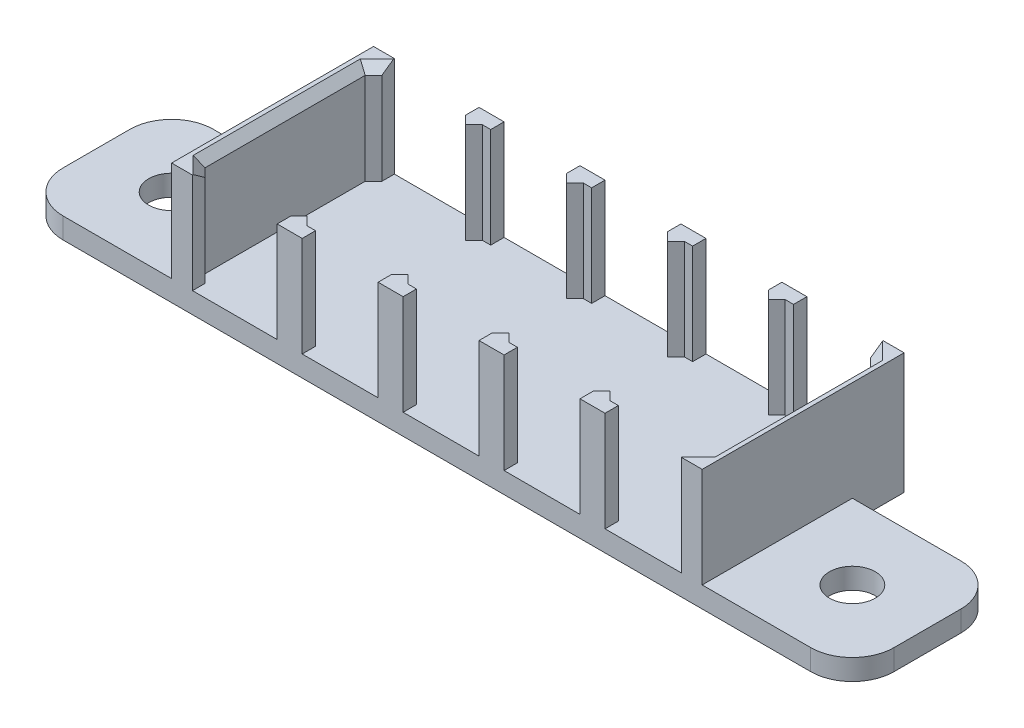
SolidWorks part; units mm, degrees
ref_plane "Спереди" through (0, 0, 0) normal (0, 0, 1) x (1, 0, 0)
ref_plane "Сверху" through (0, 0, 0) normal (0, 1, 0) x (1, 0, 0)
ref_plane "Справа" through (0, 0, 0) normal (1, 0, 0) x (0, 0, -1)
sketch "Эскиз1" plane through (0, 0, 0) normal (0, 1, 0) x (1, 0, 0)
  line L0 (0, 0) -> (0, 14.4286) construction
  line L1 (31.8, 14.4286) -> (31.8, -9.7714)
  line L2 (31.8, 14.4286) -> (-31.8, 14.4286)
  line L4 (31.8, -9.7714) -> (-31.8, -9.7714)
  line L5 (-31.8, 14.4286) -> (-31.8, -9.7714)
  point P7 (0, -9.7714)
  dimension "D1" = 31.8
  dimension "D2" = 24.2
extrude "Бобышка-Вытянуть1" add sketch "Эскиз1" along normal blind 2.5
sketch "Эскиз2" plane through (0, 0, 0) normal (0, 1, 0) x (1, 0, 0)
  line L0 (-31.8, 8.2286) -> (-49.8, -9.7714) construction
  line L1 (-31.8, -9.7714) -> (-44.8, -9.7714)
  line L2 (-31.8, -9.7714) -> (-31.8, 8.2286)
  line L3 (-31.8, 8.2286) -> (-44.8, 8.2286)
  line L4 (-49.8, -4.7714) -> (-49.8, 3.2286)
  arc A0 (-44.8, -9.7714) -> (-49.8, -4.7714) centre (-44.8, -4.7714) cw
  arc A1 (-49.8, 3.2286) -> (-44.8, 8.2286) centre (-44.8, 3.2286) cw
  circle A3 centre (-40.8, -0.7714) radius 2.75
  point P7 (-49.8, -9.7714)
  point P10 (-49.8, 8.2286)
  dimension "D3" = 5
  dimension "D4" = 5.5
  dimension "D1" = 18
  dimension "D2" = 18
extrude "Бобышка-Вытянуть2" add sketch "Эскиз2" along normal blind 2.5
mirror "Зеркальное отражение1" about plane through (0, 0, 0) normal (1, 0, 0) of "Бобышка-Вытянуть2"
sketch "Эскиз3" plane through (0, 2.5, 0) normal (0, 1, 0) x (1, 0, 0)
  line L1 (-31.8, 14.4286) -> (-30.3, 14.4286)
  line L2 (-31.8, 14.4286) -> (-31.8, -9.7714)
  line L5 (-30.3, 14.4286) -> (-29.3, 14.4286)
  line L6 (31.8, 14.4286) -> (-31.8, 14.4286) construction
  line L7 (-29.3, 14.4286) -> (-29.3, 12.9286)
  line L8 (-29.3, 12.9286) -> (-30.3, 11.9286)
  line L9 (-30.3, 14.4286) -> (-30.3, 13.0893) construction
  line L13 (-31, 2.3286) -> (-31.8, 2.3286) construction
  line L14 (-31.8, -9.7714) -> (-30.3, -9.7714)
  line L15 (-30.3, -9.7714) -> (-29.3, -9.7714)
  line L16 (-29.3, -8.2714) -> (-30.3, -7.2714)
  line L17 (-29.3, -9.7714) -> (-29.3, -8.2714)
  line L18 (-30.3, 11.9286) -> (-30.3, -7.2714)
  dimension "D1" = 1.5
  dimension "D2" = 1.5
  dimension "D3" = 1
  dimension "D4" = 135
  dimension "D5" = 24.2
extrude "Бобышка-Вытянуть3" add sketch "Эскиз3" along normal blind 12
mirror "Зеркальное отражение2" about plane through (0, 0, 0) normal (1, 0, 0) of "Бобышка-Вытянуть3"
chamfer "Фаска1" distance 1 angle 45 6 edges at (-29.8, 14.5, -12.4286) (29.8, 14.5, -12.4286) (-29.8, 14.5, 7.7714) (-30.3, 14.5, -2.3286) (29.8, 14.5, 7.7714) (30.3, 14.5, -2.3286)
sketch "Эскиз4" plane through (0, 2.5, 0) normal (0, 1, 0) x (1, 0, 0)
  line L0 (-30.3, -17.4714) -> (-30.3, -9.7714) construction
  line L2 (-30.3, -9.7714) -> (-18.15, -9.7714) construction
  line L4 (-18.15, -9.7714) -> (-19.15, -9.7714)
  line L5 (-19.15, -9.7714) -> (-19.15, -8.1714)
  line L6 (-19.15, -8.1714) -> (-18.15, -8.1714) construction
  line L7 (-18.15, -8.1714) -> (-18.15, -7.1714) construction
  line L8 (-19.15, -8.1714) -> (-18.15, -7.1714)
  line L9 (-18.15, -8.1714) -> (-17.15, -8.1714) construction
  line L10 (-18.15, -7.1714) -> (-17.15, -8.1714)
  line L11 (-17.15, -8.1714) -> (-16.15, -8.1714)
  line L12 (-16.15, -8.1714) -> (-16.15, -9.7714)
  line L13 (-16.15, -9.7714) -> (-18.15, -9.7714)
  line L14 (-44.8, -9.7714) -> (-31.8, -9.7714) construction
  line L16 (-30.3, -7.2714) -> (-30.3, 11.9286) construction
  dimension "D1" = 12.15
  dimension "D2" = 1
  dimension "D3" = 1.6
  dimension "D4" = 1
  dimension "D5" = 1
  dimension "D6" = 1
  dimension "D7" = 1
extrude "Бобышка-Вытянуть4" add sketch "Эскиз4" along normal blind 12
ref_plane "Плоскость1" through (0, 0, -2.3286) normal (0, 0, 1) x (1, 0, 0)
mirror "Зеркальное отражение3" about plane through (0, 0, -2.3286) normal (0, 0, 1) of "Бобышка-Вытянуть4"
pattern_linear "Линейный массив1" count 4 spacing 12.1 along (1, 0, 0) of "Зеркальное отражение3"
ref_plane "Плоскость2" through (0, 0, 0.7714) normal (0, 0, 1) x (1, 0, 0)
